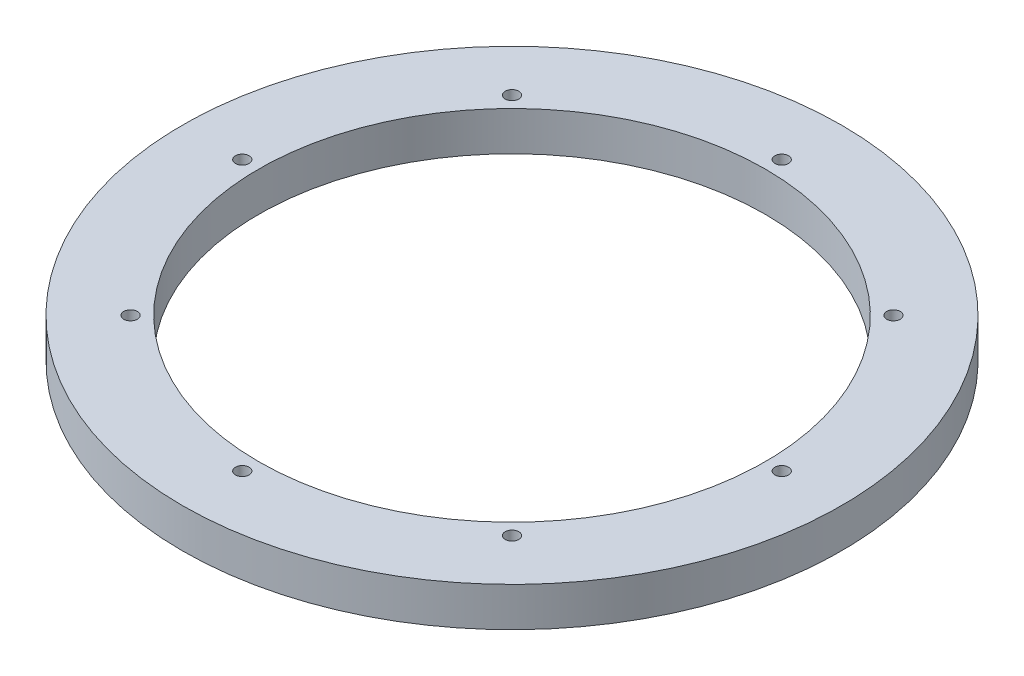
SolidWorks part; units mm, degrees
material "6061 Alloy"
ref_plane "Front Plane" through (0, 0, 0) normal (0, 0, 1) x (1, 0, 0)
ref_plane "Top Plane" through (0, 0, 0) normal (0, 1, 0) x (1, 0, 0)
ref_plane "Right Plane" through (0, 0, 0) normal (1, 0, 0) x (0, 0, -1)
sketch "Sketch1" plane through (0, 0, 0) normal (0, 1, 0) x (1, 0, 0)
  circle A0 centre (0, 0) radius 49.2125
  circle A1 centre (0, 0) radius 64.008
  circle A3 centre (0, -52.3875) radius 1.3208
  circle A4 centre (-37.0436, -37.0436) radius 1.3208
  circle A5 centre (-52.3875, 0) radius 1.3208
  circle A6 centre (-37.0436, 37.0436) radius 1.3208
  circle A7 centre (0, 52.3875) radius 1.3208
  circle A8 centre (37.0436, 37.0436) radius 1.3208
  circle A9 centre (52.3875, 0) radius 1.3208
  circle A10 centre (37.0436, -37.0436) radius 1.3208
  point P21 (0, 0)
  dimension "D1" = 98.425
  dimension "D4" = 2.6416
  dimension "D5" = 52.3875
  dimension "D2" = 14.7955
  dimension "D6" = 8
extrude "Boss-Extrude1" add sketch "Sketch1" along normal blind 7.62 contours A0 | A1 region at (-62.1976, 0, 0)
equation "\"Middle Coupler Inner Daimeter\"= 3.875in"
equation "\"Middle Coupler  Wall Thickness\" = 0.25in"
equation "\"Middle Coupler Bottom Thickness\"= 0.2in"
equation "\"Bearing Rail Offset\"= 0.45in"
equation "\"3-56 UNF Tap\"= 0.089in"
equation "\"3-56 UNF Clearance\"= 0.104in"
equation "\"D5@Sketch1\"=(\"Middle Coupler Inner Daimeter\"*2+0.5)/4in"
equation "\"Ball Bearing Distance\"= 0.03in"
equation "\"D4@Sketch1\"=\"3-56 UNF Clearance\""
equation "\"D1@Sketch1\"=\"Middle Coupler Inner Daimeter\""
equation "\"TCA Outer Diameter\" = 6in"
equation "\"Interstage Aeroframe Wall Thickness\" = 0.072in"
equation "\"Compression Spring OD\"= 0.42in"
equation "\"10-24 Tap\"= 0.157in"
equation "\"10-24 Clearance\"= 0.196in"
equation "\"Lower Stage Fuselage Wall Thickness\" = 0.25in"
equation "\"6-32 Tap\" = 0.107in"
equation "\"1/4-20 Tap\" = 0.201in"
equation "\"D2@Sketch1\"=0.5875 - 5/1000"
